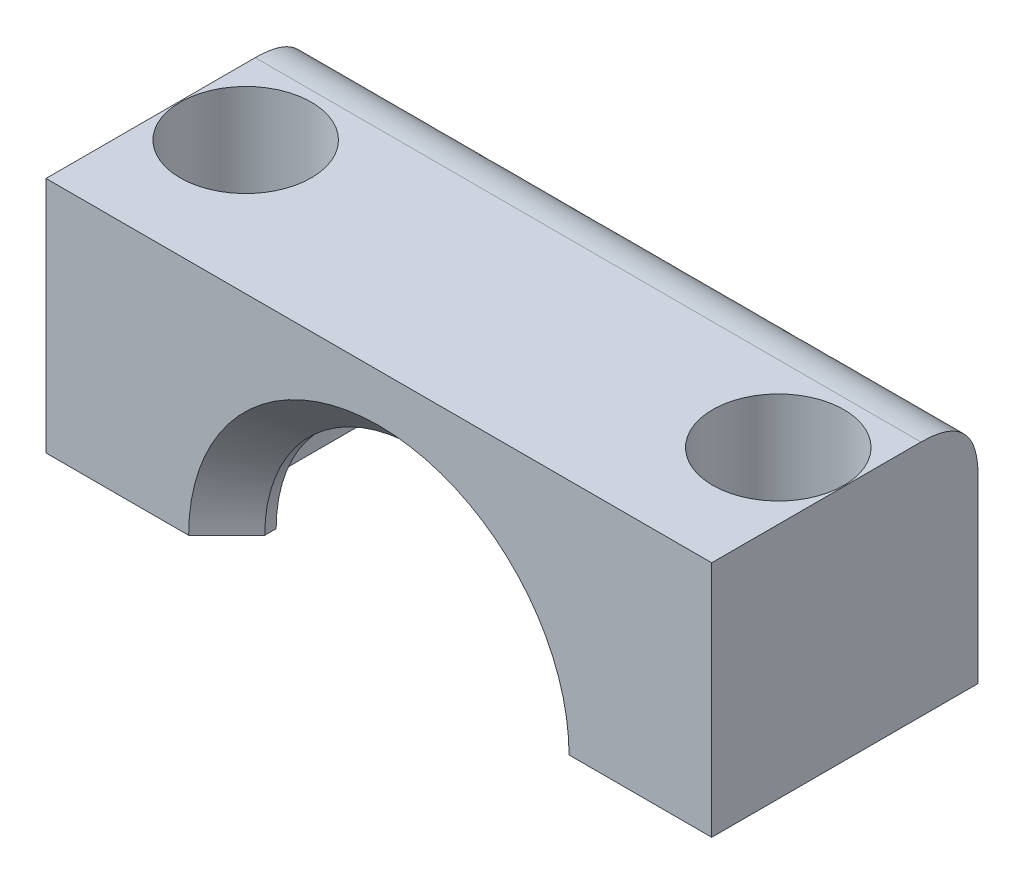
SolidWorks part; units mm, degrees
ref_plane "Спереди" through (0, 0, 0) normal (0, 0, 1) x (1, 0, 0)
ref_plane "Сверху" through (0, 0, 0) normal (0, 1, 0) x (1, 0, 0)
ref_plane "Справа" through (0, 0, 0) normal (1, 0, 0) x (0, 0, -1)
sketch "Эскиз2" plane through (0, 0, 0) normal (0, 0, 1) x (1, 0, 0)
  line L1 (-8.75, 0) -> (8.75, 0)
  line L2 (-8.75, 0) -> (-8.75, 6.25)
  line L3 (-8.75, 6.25) -> (8.75, 6.25)
  line L4 (8.75, 0) -> (8.75, 6.25)
  point P4 (0, 0)
  dimension "D1" = 17.5
  dimension "D2" = 6.25
extrude "тело" add sketch "Эскиз2" along normal blind 3.5 and the other way blind 3.5
sketch "Эскиз3" plane through (0, 0, 3.5) normal (0, 0, 1) x (1, 0, 0)
  line L0 (-8.75, 0) -> (8.75, 0) construction
  circle A0 centre (0, 0) radius 4
  dimension "D1" = 8
extrude "вырез под гайки" cut sketch "Эскиз3" against normal through all
sketch "Эскиз4" plane through (0, 0, 0) normal (0, 0, 1) x (1, 0, 0)
  circle A0 centre (0, 0) radius 5.25
  dimension "D1" = 10.5
extrude "вырез под подшипник" cut sketch "Эскиз4" against normal blind 2.2 and the other way blind 2.2
sketch "Эскиз5" plane through (0, 6.25, 0) normal (0, 1, 0) x (1, 0, 0)
  line L0 (-7, 0) -> (7, 0) construction
  circle A0 centre (-7, 0) radius 1
  circle A1 centre (7, 0) radius 1
  point P4 (0, 0)
  dimension "D1" = 2
  dimension "D2" = 14
extrude "крепежные отверстия" cut sketch "Эскиз5" against normal through all
chamfer "Фаска2" distance 1 angle 45 2 edges at (0, 4, -3.5) (0, 4, 3.5)
fillet "Скругление1" radius 1.5 1 edges at (0, 6.25, -3.5) conic rho 0.5
sketch "Эскиз6" plane through (0, 6.25, 0) normal (0, 1, 0) x (1, 0, 0)
  circle A0 centre (-7, 0) radius 1.725
  circle A1 centre (7, 0) radius 1.725
  dimension "D1" = 3.45
extrude "Углубления под шляпки" cut sketch "Эскиз6" against normal blind 3.5
